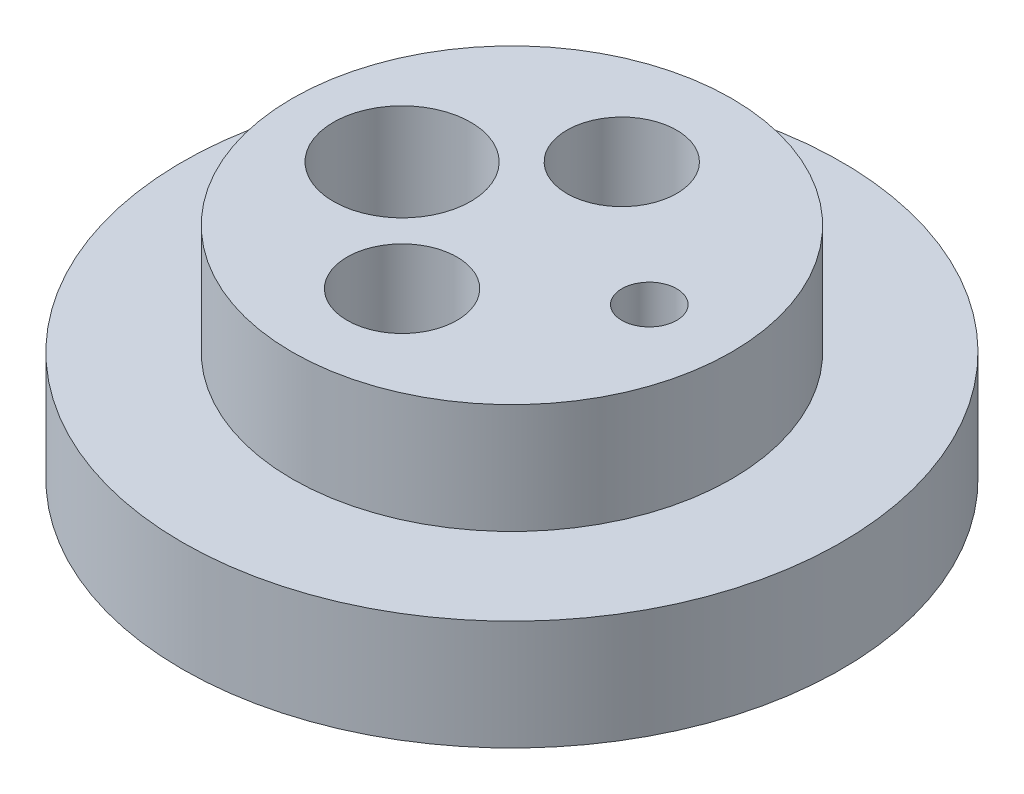
SolidWorks part; units mm, degrees
ref_plane "前视基准面" through (0, 0, 0) normal (0, 0, 1) x (1, 0, 0)
ref_plane "上视基准面" through (0, 0, 0) normal (0, 1, 0) x (1, 0, 0)
ref_plane "右视基准面" through (0, 0, 0) normal (1, 0, 0) x (0, 0, -1)
other "Configuration Table"
sketch "草图1" plane through (0, 0, 0) normal (0, 1, 0) x (1, 0, 0)
  circle A0 centre (0, 0) radius 24
  dimension "D1" = 48
extrude "凸台-拉伸1" add sketch "草图1" along normal blind 8
sketch "草图2" plane through (0, 8, 0) normal (0, 1, 0) x (1, 0, 0)
  circle A0 centre (0, 0) radius 16
  dimension "D1" = 32
extrude "凸台-拉伸2" add sketch "草图2" along normal blind 8
sketch "草图4" plane through (0, 16, 0) normal (0, 1, 0) x (1, 0, 0)
  line L0 (-16, 0) -> (16, 0) construction
  line L1 (0, 16) -> (0, -16) construction
  circle A0 centre (0, 0) radius 16 construction
  circle A1 centre (0, 0) radius 16 construction
  circle A2 centre (-8, 0) radius 5
  circle A3 centre (0, 8) radius 4
  circle A4 centre (0, -8) radius 4
  circle A5 centre (10, 0) radius 2
  dimension "D1" = 10
  dimension "D2" = 8
  dimension "D3" = 8
  dimension "D4" = 4
  dimension "D5" = 8
  dimension "D6" = 8
  dimension "D7" = 8
  dimension "D8" = 6
extrude "切除-拉伸1" cut sketch "草图4" against normal through all
